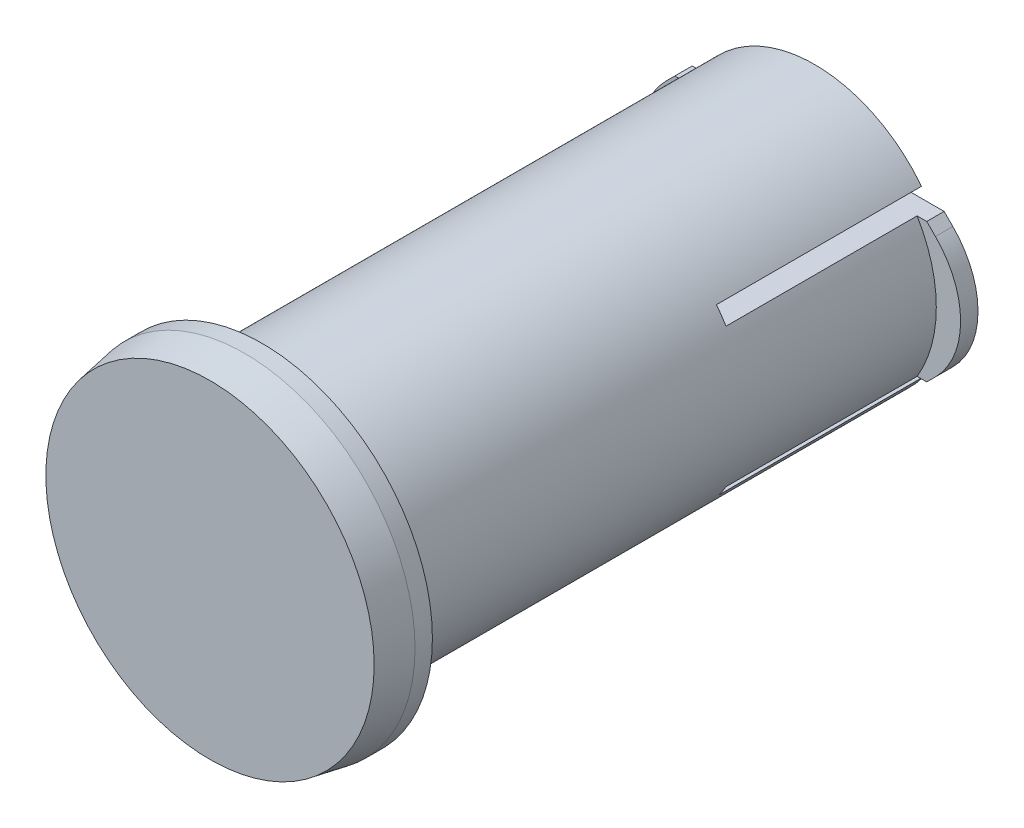
SolidWorks part; units mm, degrees
ref_plane "Front Plane" through (0, 0, 0) normal (0, 0, 1) x (1, 0, 0)
ref_plane "Top Plane" through (0, 0, 0) normal (0, 1, 0) x (1, 0, 0)
ref_plane "Right Plane" through (0, 0, 0) normal (1, 0, 0) x (0, 0, -1)
sketch "Sketch1" plane through (0, 0, 0) normal (0, 0, 1) x (1, 0, 0)
  circle A0 centre (0, 0) radius 3.9
  circle A1 centre (0, 0) radius 4.9
  dimension "D1" = 7.8
  dimension "D2" = 1
extrude "Boss-Extrude1" add sketch "Sketch1" against normal blind 16 contours A0
extrude "Boss-Extrude2" add sketch "Sketch1<3>" along normal blind 1.5 contours A1
sketch "Sketch1<3>" plane through (0, 0, 0) normal (0, 0, 1) x (1, 0, 0) same geometry as "Sketch1"
sketch "Sketch5" plane through (0, 0, 0) normal (0, 0, -1) x (-1, 0, 0)
  circle A0 centre (0, 0) radius 2
  circle A1 centre (0, 0) radius 3.9 construction
  circle A2 centre (0, 0) radius 3.9
  dimension "D1" = 4
extrude "Cut-Extrude2" cut sketch "Sketch5" along normal blind 3.2 from offset 15.9
chamfer "Chamfer1" distance 1 angle 10 1 edges at (4.9, 0, 1.5) first distance on face at (4.9, 0, 1.5)
sketch "Sketch2" plane through (0, 0, -16) normal (0, 0, -1) x (-1, 0, 0)
  line L0 (-3.9, 0) -> (3.9, 0) construction
  line L2 (-3.6251, 2) -> (-2.1, 2)
  line L4 (-3.6251, -2) -> (-2.1, -2)
  line L5 (-2.1, 2) -> (-2.1, -2)
  line L6 (-3.6251, -2) -> (-3.8751, -1.75)
  line L7 (-3.6251, 2) -> (-3.8751, 1.75)
  circle A0 centre (0, 0) radius 3.9 construction
  arc A3 (-3.8751, 1.75) -> (-3.8751, -1.75) centre (-2.1251, 0) ccw
  point P0 (-2.85, 0)
  point P6 (0, 0)
  point P17 (-4.6, 0)
  dimension "D3" = 45
  dimension "D6" = 2.4749
  dimension "D4" = 0.25
  dimension "D7" = 0.7
  dimension "D1" = 2.85
  dimension "D2" = 1.8
  dimension "D5" = 4
extrude "Boss-Extrude3" add sketch "Sketch2" against normal blind 0.5
sketch "Sketch4" plane through (0, 0, -16) normal (0, 0, -1) x (-1, 0, 0)
  line L1 (-3.6251, -2) -> (-2.1, -2) construction
  line L2 (-3.6251, 2) -> (-2.1, 2) construction
  line L3 (-2.1, 2) -> (-2.1, -2) construction
  line L4 (-3.9, 0) -> (3.9, 0) construction
  line L5 (-3.6251, -2) -> (-2.1, -2)
  line L6 (-3.6251, 2) -> (-2.1, 2)
  line L7 (-2.1, 2) -> (-2.1, -2)
  line L8 (-3.9, 0) -> (3.9, 0) construction
  line L9 (-3.6251, 2.4) -> (-1.2, 2.4)
  line L10 (-1.2, 2.4) -> (-1.2, -2.3)
  line L11 (-3.6251, -2.3) -> (-1.2, -2.3)
  line L12 (-3.6251, 2.4) -> (-3.6251, 2)
  line L13 (-3.6251, -2) -> (-3.6251, -2.3)
  dimension "D2" = 0.9
  dimension "D1" = 0.4
  dimension "D3" = 0.3
extrude "Cut-Extrude1" cut sketch "Sketch4" against normal blind 6 contours L9 L10 L11 L13 L5 L7 L6 L12
fillet "Fillet1" [suppressed] radius 0.2
chamfer "Chamfer2" [suppressed] distance 1 angle 10
mirror "Mirror1" about plane through (0, 0, 0) normal (1, 0, 0) of "Chamfer2", "Fillet1", "Cut-Extrude1", "Boss-Extrude3"
